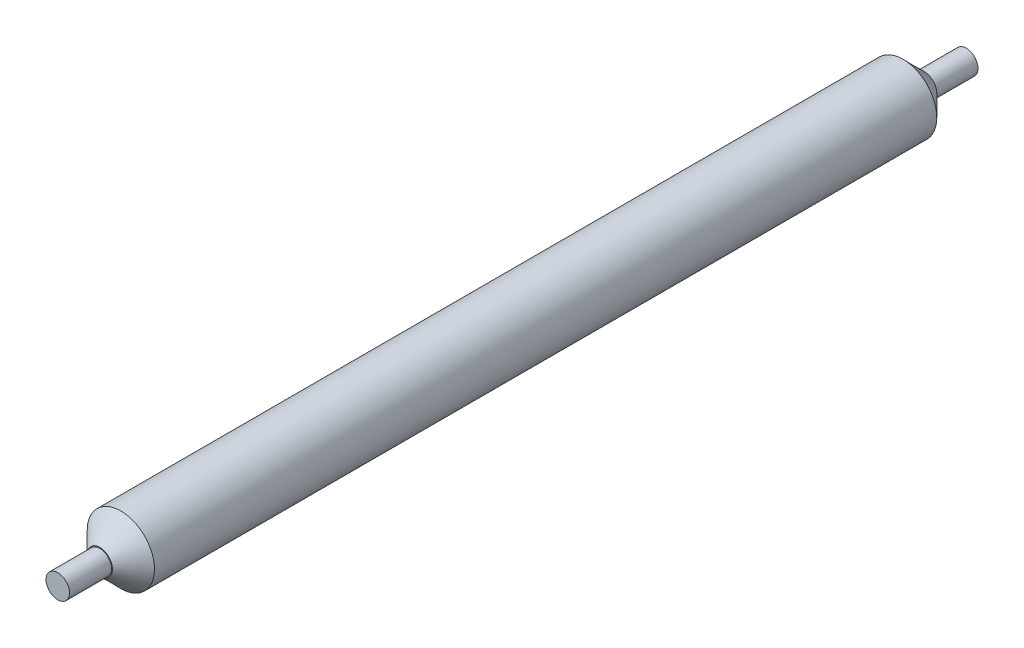
SolidWorks part; units mm, degrees
ref_plane "Płaszczyzna przednia" through (0, 0, 0) normal (0, 0, 1) x (1, 0, 0)
ref_plane "Płaszczyzna górna" through (0, 0, 0) normal (0, 1, 0) x (1, 0, 0)
ref_plane "Płaszczyzna prawa" through (0, 0, 0) normal (1, 0, 0) x (0, 0, -1)
sketch "Szkic1" plane through (0, 0, 0) normal (0, 0, 1) x (1, 0, 0)
  circle A0 centre (0, 0) radius 1.4
extrude "Dodanie-wyciągnięcie1" add sketch "Szkic1" along normal blind 54 and the other way blind 54 contours A0
sketch "Szkic2" plane through (0, 0, 0) normal (0, 0, 1) x (1, 0, 0)
  circle A0 centre (0, 0) radius 4
extrude "Dodanie-wyciągnięcie2" add sketch "Szkic2" along normal blind 49 and the other way blind 49
chamfer "Sfazowanie4" distance 2.5 angle 45 2 edges at (4, 0, -49) (4, 0, 49)
